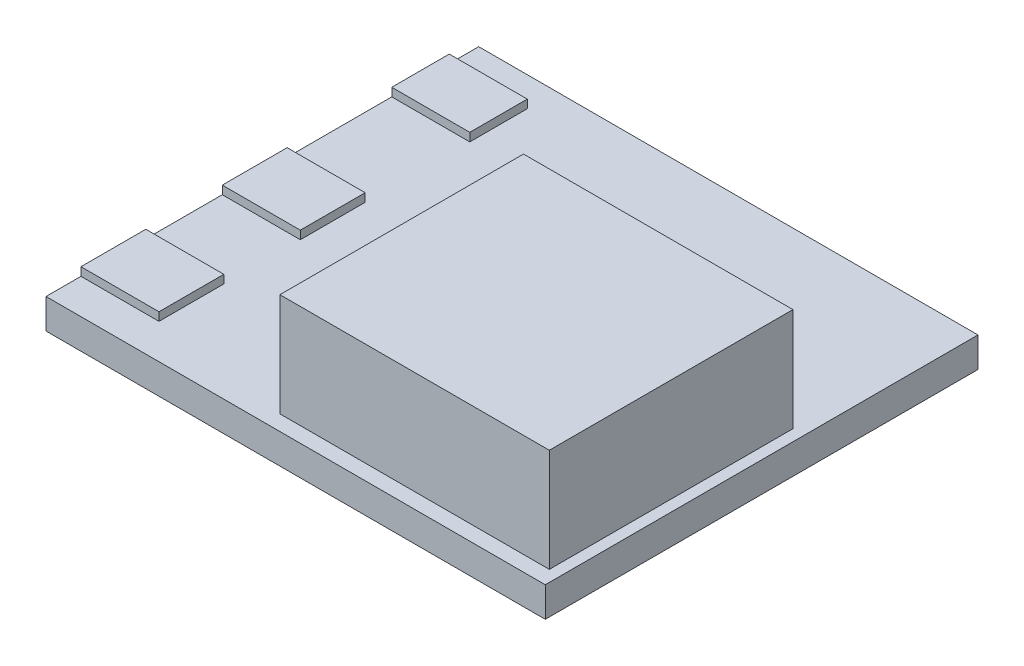
SolidWorks part; units mm, degrees
ref_plane "Front Plane" through (0, 0, 0) normal (0, 0, 1) x (1, 0, 0)
ref_plane "Top Plane" through (0, 0, 0) normal (0, 1, 0) x (1, 0, 0)
ref_plane "Right Plane" through (0, 0, 0) normal (1, 0, 0) x (0, 0, -1)
sketch "Sketch1" plane through (0, 0, 0) normal (0, 1, 0) x (1, 0, 0)
  line L1 (0, 0) -> (30, 0)
  line L2 (0, 0) -> (0, 26)
  line L3 (0, 26) -> (30, 26)
  line L4 (30, 0) -> (30, 26)
  line L5 (29.3215, 0.9208) -> (13.1341, 0.9208)
  line L6 (29.3215, 0.9208) -> (29.3215, 15.5574)
  line L7 (29.3215, 15.5574) -> (13.1341, 15.5574)
  line L8 (13.1341, 0.9208) -> (13.1341, 15.5574)
  dimension "D1" = 30
  dimension "D2" = 26
extrude "Boss-Extrude1" add sketch "Sketch1" along normal blind 1.8 contours L8 L5 L6 L7 | L1 L4 L3 L2 L5 L8 L7 L6 region at (12.283, 0, -15.077) region at (21.2278, 0, -8.2391)
extrude "Boss-Extrude2" add sketch "Sketch1<3>" along normal blind 8 contours L8 L5 L6 L7 region at (21.2278, 0, -8.2391)
sketch "Sketch1<3>" plane through (0, 0, 0) normal (0, 1, 0) x (1, 0, 0) same geometry as "Sketch1"
sketch "Sketch2" plane through (0, 1.8, 0) normal (0, 1, 0) x (1, 0, 0)
  line L0 (0, 0) -> (0, 26) construction
  line L1 (0, 24.2308) -> (4.6883, 24.2308)
  line L2 (0, 24.2308) -> (0, 20.7751)
  line L3 (0, 20.7751) -> (4.6883, 20.7751)
  line L4 (4.6883, 24.2308) -> (4.6883, 20.7751)
  line L6 (0, 14.4889) -> (4.6883, 14.4889)
  line L7 (0, 14.4889) -> (0, 10.5921)
  line L8 (0, 10.5921) -> (4.6883, 10.5921)
  line L9 (4.6883, 14.4889) -> (4.6883, 10.5921)
  line L10 (0, 5.9969) -> (4.6883, 5.9969)
  line L11 (0, 5.9969) -> (0, 2.1001)
  line L12 (0, 2.1001) -> (4.6883, 2.1001)
  line L13 (4.6883, 5.9969) -> (4.6883, 2.1001)
extrude "Boss-Extrude3" add sketch "Sketch2" along normal blind 0.5
